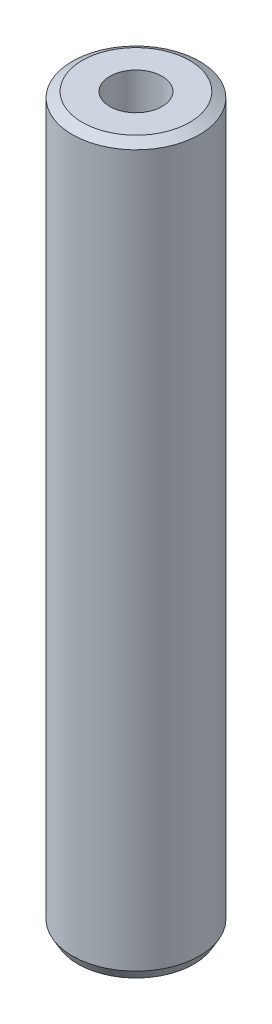
SolidWorks part; units mm, degrees
ref_plane "Front Plane" through (0, 0, 0) normal (0, 0, 1) x (1, 0, 0)
ref_plane "Top Plane" through (0, 0, 0) normal (0, 1, 0) x (1, 0, 0)
ref_plane "Right Plane" through (0, 0, 0) normal (1, 0, 0) x (0, 0, -1)
sketch "Sketch1" plane through (0, 0, 0) normal (0, 1, 0) x (1, 0, 0)
  circle A0 centre (0, 0) radius 52.5
  dimension "SHAFT_OD" = 105
extrude "Boss-Extrude1" add sketch "Sketch1" along normal blind 600
sketch "Sketch2" plane through (0, 0, 0) normal (0, 1, 0) x (1, 0, 0)
  circle A0 centre (0, 0) radius 21.6081
  dimension "BORE_D" = 43.2162
extrude "Cut-Extrude1" cut sketch "Sketch2" along normal through all
chamfer "Chamfer1" distance 4.6564 angle 60.364 2 edges at (0, 600, 52.5) (0, 0, 52.5) first distance on face at (0, 600, 52.5) first distance on face at (0, 0, 21.6081)
